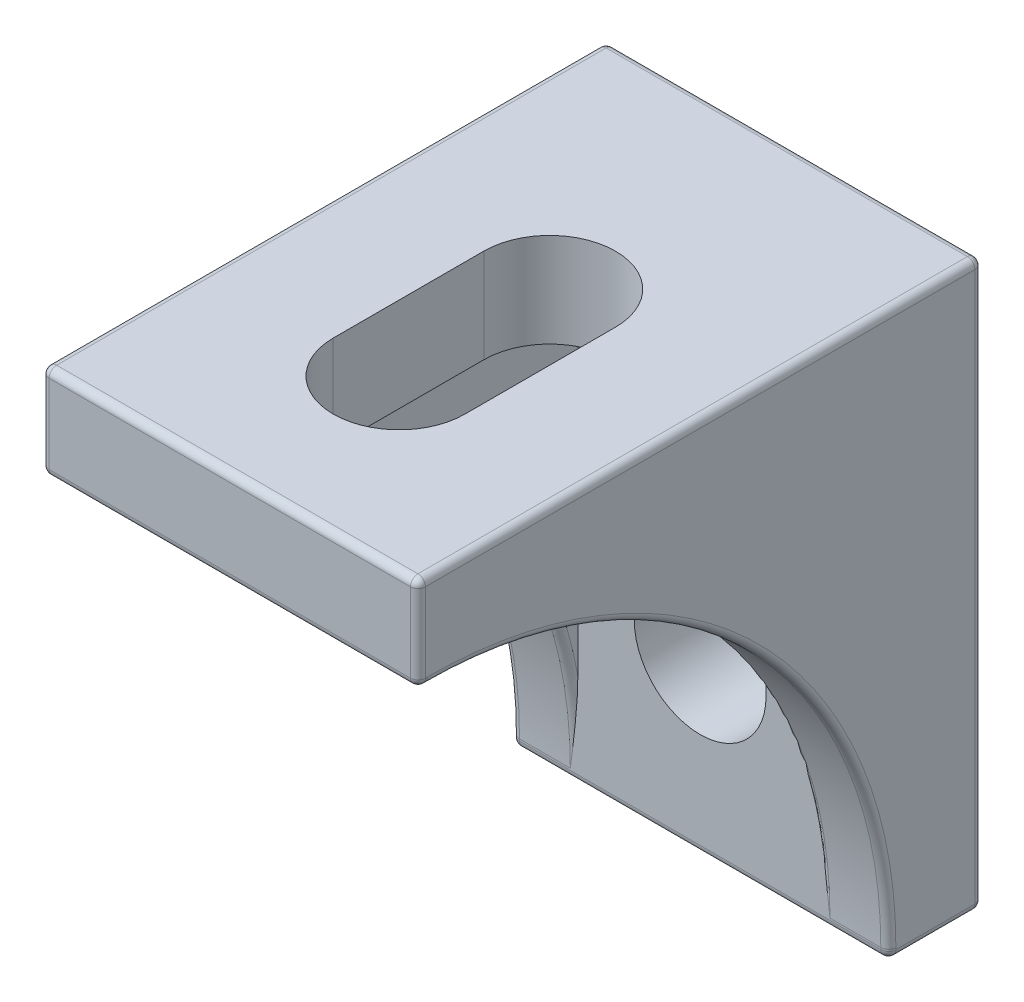
SolidWorks part; units mm, degrees
ref_plane "정면" through (0, 0, 0) normal (0, 0, 1) x (1, 0, 0)
ref_plane "윗면" through (0, 0, 0) normal (0, 1, 0) x (1, 0, 0)
ref_plane "우측면" through (0, 0, 0) normal (1, 0, 0) x (0, 0, -1)
sketch "스케치1" plane through (0, 0, 0) normal (0, 0, 1) x (1, 0, 0)
  line L0 (10, -13) -> (10, -21) construction
  line L1 (0, 0) -> (20, 0)
  line L2 (0, 0) -> (0, -30)
  line L3 (0, -30) -> (20, -30)
  line L4 (20, 0) -> (20, -30)
  line L5 (13.5, -13) -> (13.5, -21)
  line L6 (6.5, -13) -> (6.5, -21)
  line L7 (0, -5) -> (20, -5)
  arc A0 (13.5, -13) -> (6.5, -13) centre (10, -13) ccw
  arc A1 (6.5, -21) -> (13.5, -21) centre (10, -21) ccw
  point P7 (10, -17)
  dimension "D5" = 13
  dimension "D1" = 30
  dimension "D2" = 20
  dimension "D3" = 7
  dimension "D4" = 10
  dimension "D6" = 8
  dimension "D7" = 5
extrude "보스-돌출1" add sketch "스케치1" along normal blind 5 contours L7 L2 L3 L4 A1 L6 A0 L5 region at (10, -5.3202, 0)
extrude "보스-돌출2" add sketch "스케치1<3>" along normal blind 30 contours L2 L7 L4 L1 region at (10, -2.5, 0)
sketch "스케치1<3>" plane through (0, 0, 0) normal (0, 0, 1) x (1, 0, 0) same geometry as "스케치1"
sketch "스케치2" plane through (0, 0, 0) normal (0, 1, 0) x (1, 0, 0)
  line L0 (10, -13) -> (10, -21) construction
  line L1 (13.5, -13) -> (13.5, -21)
  line L2 (6.5, -13) -> (6.5, -21)
  line L4 (20, -30) -> (20, 0) construction
  line L6 (0, -30) -> (20, -30) construction
  arc A0 (13.5, -13) -> (6.5, -13) centre (10, -13) ccw
  arc A1 (6.5, -21) -> (13.5, -21) centre (10, -21) ccw
  point P2 (10, -17)
  point P7 (0, 0)
  dimension "D1" = 7
  dimension "D2" = 8
  dimension "D3" = 10
  dimension "D4" = 13
sketch "스케치3" plane through (0, 0, 0) normal (-1, 0, 0) x (0, 0, 1)
  line L0 (5, -30) -> (0, -30) construction
  line L1 (29.5, -5) -> (29.9829, -5)
  line L2 (5, -29.5) -> (5, -30)
  line L6 (5, -5) -> (5, -29.5)
  arc A0 (29.5, -5) -> (5, -29.5) centre (29.5, -29.5) ccw
  point P13 (5, -5)
  line M8 (5, -30) -> (5, -5)
  line M9 (5, -5) -> (30, -5)
  dimension "D1" = 24.5
extrude "보스-돌출3" add sketch "스케치3" against normal blind 20 contours A0 M9 M8 region at (0, -10.4725, 10.4725)
extrude "컷-돌출2" cut sketch "스케치1<4>" against normal through all and the other way through all contours L5 A1 L6 A0
sketch "스케치1<4>" plane through (0, 0, 0) normal (0, 0, 1) x (1, 0, 0) same geometry as "스케치1"
extrude "컷-돌출3" cut sketch "스케치2" against normal blind 20 contours A1 L1 A0 L2
sketch "스케치4" plane through (0, 0, 30) normal (0, 0, 1) x (1, 0, 0)
  line L2 (0, -30) -> (20, -30) construction
  line L3 (15.0141, -30) -> (15.0141, -29.9771)
  line L10 (0, -5) -> (20, -5) construction
  line L11 (16.5, -5) -> (3.5, -5)
  line L12 (16.5, -5) -> (16.5, -30)
  line L13 (16.5, -30) -> (3.5, -30)
  line L14 (3.5, -5) -> (3.5, -30)
  line L15 (20, 0) -> (20, -30) construction
  line L16 (0, 0) -> (0, -30) construction
  line M6 (0, -5) -> (20, -5)
  dimension "D1" = 3.5
  dimension "D2" = 3.5
extrude "컷-돌출5" cut sketch "스케치4" against normal blind 25 contours L14 L13 L12 M6 region at (10, -17.5, 30)
fillet "필렛3" radius 0.4 8 edges at (20, -5, 29.75) (20, -29.75, 5) (20, -12.1759, 12.1759) (3.5, -12.1759, 12.1759) (16.5, -12.1759, 12.1759) (0, -5, 29.75) (0, -29.75, 5) (0, -12.1759, 12.1759)
fillet "필렛4" radius 0.4 13 edges at (0, -30, 2.3) (0.1172, -30, 4.8828) (20, -30, 2.3) (19.8828, -30, 4.8828) (0, -2.3, 30) (0.1172, -4.8828, 30) (20, -2.3, 30) (19.8828, -4.8828, 30) (10, -30, 5) (10, -5, 30) (10, 0, 30) (0, 0, 15) (20, 0, 15)
fillet "필렛5" radius 0.4 8 edges at (0.1172, -0.1172, 0) (0.1172, -29.8828, 0) (10, -30, 0) (19.8828, -29.8828, 0) (19.8828, -0.1172, 0) (0, -15, 0) (20, -15, 0) (10, 0, 0)
